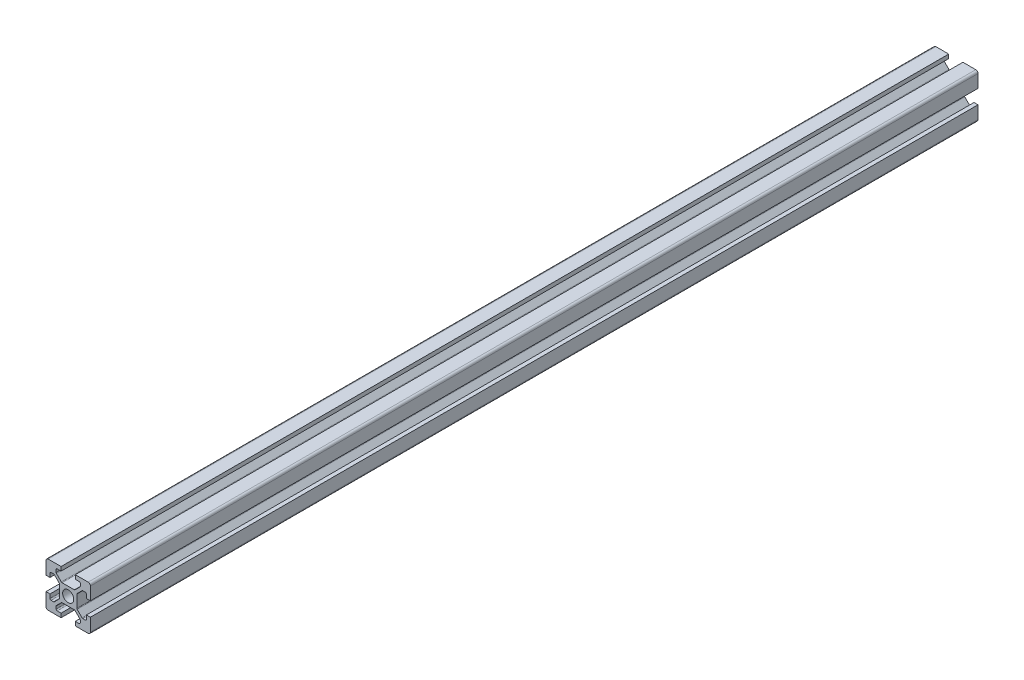
SolidWorks part; units mm, degrees
material "1060 Alloy"
ref_plane "Front Plane" through (0, 0, 0) normal (0, 0, 1) x (1, 0, 0)
ref_plane "Top Plane" through (0, 0, 0) normal (0, 1, 0) x (1, 0, 0)
ref_plane "Right Plane" through (0, 0, 0) normal (1, 0, 0) x (0, 0, -1)
sketch "Sketch1" plane through (0, 0, 0) normal (0, 0, 1) x (1, 0, 0)
  line L0 (20, 0) -> (-8.059, 28.059) construction
  line L1 (0, 0) -> (6.8, 0)
  line L2 (0, 0) -> (0, 6.8)
  line L3 (0, 20) -> (6.8, 20)
  line L4 (20, 0) -> (20, 6.8)
  line L5 (6.8, 20) -> (6.8, 18.2)
  line L6 (20, 20) -> (8.2322, 8.2322) construction
  line L7 (12.95, 6.1) -> (7.05, 6.1)
  line L8 (13.9, 7.05) -> (13.9, 12.95)
  line L9 (12.95, 13.9) -> (7.05, 13.9)
  line L10 (6.1, 7.05) -> (6.1, 12.95)
  line L11 (13.9, 6.1) -> (6.1, 13.9) construction
  line L12 (13.9, 13.9) -> (6.1, 6.1) construction
  line L13 (4.55, 16.4) -> (7.05, 13.9)
  line L14 (13.2, 18.2) -> (13.2, 20)
  line L15 (1.8, 6.8) -> (0, 6.8)
  line L16 (0, 13.2) -> (0, 20)
  line L17 (0, 13.2) -> (1.8, 13.2)
  line L18 (10, 10) -> (10, 13.9) construction
  line L19 (16.4, 4.55) -> (13.9, 7.05)
  line L20 (4.55, 16.4) -> (4.55, 18.2)
  line L21 (4.55, 18.2) -> (6.8, 18.2)
  line L22 (13.2, 18.2) -> (15.45, 18.2)
  line L23 (15.45, 18.2) -> (15.45, 16.4)
  line L24 (15.45, 16.4) -> (12.95, 13.9)
  line L25 (16.4, 4.55) -> (18.2, 4.55)
  line L26 (18.2, 4.55) -> (18.2, 6.8)
  line L27 (20, 6.8) -> (18.2, 6.8)
  line L28 (18.2, 13.2) -> (20, 13.2)
  line L29 (18.2, 13.2) -> (18.2, 15.45)
  line L30 (18.2, 15.45) -> (16.4, 15.45)
  line L31 (16.4, 15.45) -> (13.9, 12.95)
  line L32 (1.8, 4.55) -> (3.6, 4.55)
  line L33 (3.6, 15.45) -> (6.1, 12.95)
  line L34 (3.6, 15.45) -> (1.8, 15.45)
  line L35 (1.8, 15.45) -> (1.8, 13.2)
  line L36 (0, 13.2) -> (1.8, 13.2)
  line L37 (1.8, 6.8) -> (0, 6.8)
  line L38 (3.6, 4.55) -> (6.1, 7.05)
  line L39 (1.8, 6.8) -> (1.8, 4.55)
  line L40 (15.45, 3.6) -> (12.95, 6.1)
  line L41 (4.55, 3.6) -> (7.05, 6.1)
  line L42 (4.55, 1.8) -> (4.55, 3.6)
  line L43 (6.8, 1.8) -> (4.55, 1.8)
  line L44 (6.8, 1.8) -> (6.8, 0)
  line L45 (15.45, 3.6) -> (15.45, 1.8)
  line L46 (15.45, 1.8) -> (13.2, 1.8)
  line L47 (13.2, 0) -> (13.2, 1.8)
  line L48 (13.2, 20) -> (20, 20)
  line L49 (20, 13.2) -> (20, 20)
  line L50 (13.2, 0) -> (20, 0)
  line L51 (6.1, 6.1) -> (-5.5045, -5.5045) construction
  circle A0 centre (10, 10) radius 2.5
  point P25 (10, 16.4)
  point P39 (13.2, 19.1)
  point P46 (0.9, 6.8)
  dimension "D3" = 5
  dimension "D2" = 20
  dimension "D4" = 7.8
  dimension "D5" = 7.8
  dimension "D6" = 6.8
  dimension "D7" = 6.8
  dimension "D8" = 1.8
  dimension "D9" = 10.9
  dimension "D10" = 1.8
  dimension "D11" = 10.9
  dimension "D12" = 20
extrude "Boss-Extrude1" add sketch "Sketch1" along normal blind 400 contours L47 L50 L4 L27 L26 L25 L19 L8 L31 L30 L29 L28 L49 L48 L14 L22 L23 L24 L9 L13 L20 L21 L5 L3 L16 L17 L35 L34 L33 L10 L38 L32 L39 L15 L2 L1 L44 L43 L42 L41 L7 L40 L45 L46 A0 region at (0.2828, 3.4, 0)
fillet "Fillet1" radius 1 4 edges at (20, 20, 200) (20, 0, 200) (0, 0, 200) (0, 20, 200)
fillet "Fillet2" radius 0.5 6 edges at (4.55, 18.2, 200) (4.55, 16.4, 200) (7.05, 13.9, 200) (15.45, 18.2, 200) (15.45, 16.4, 200) (12.95, 13.9, 200)
fillet "Fillet3" radius 0.5 6 edges at (18.2, 15.45, 200) (16.4, 15.45, 200) (13.9, 12.95, 200) (18.2, 4.55, 200) (13.9, 7.05, 200) (16.4, 4.55, 200)
fillet "Fillet4" radius 0.5 6 edges at (1.8, 15.45, 200) (3.6, 15.45, 200) (6.1, 12.95, 200) (3.6, 4.55, 200) (1.8, 4.55, 200) (6.1, 7.05, 200)
fillet "Fillet5" radius 0.5 6 edges at (7.05, 6.1, 200) (4.55, 3.6, 200) (4.55, 1.8, 200) (15.45, 1.8, 200) (15.45, 3.6, 200) (12.95, 6.1, 200)
